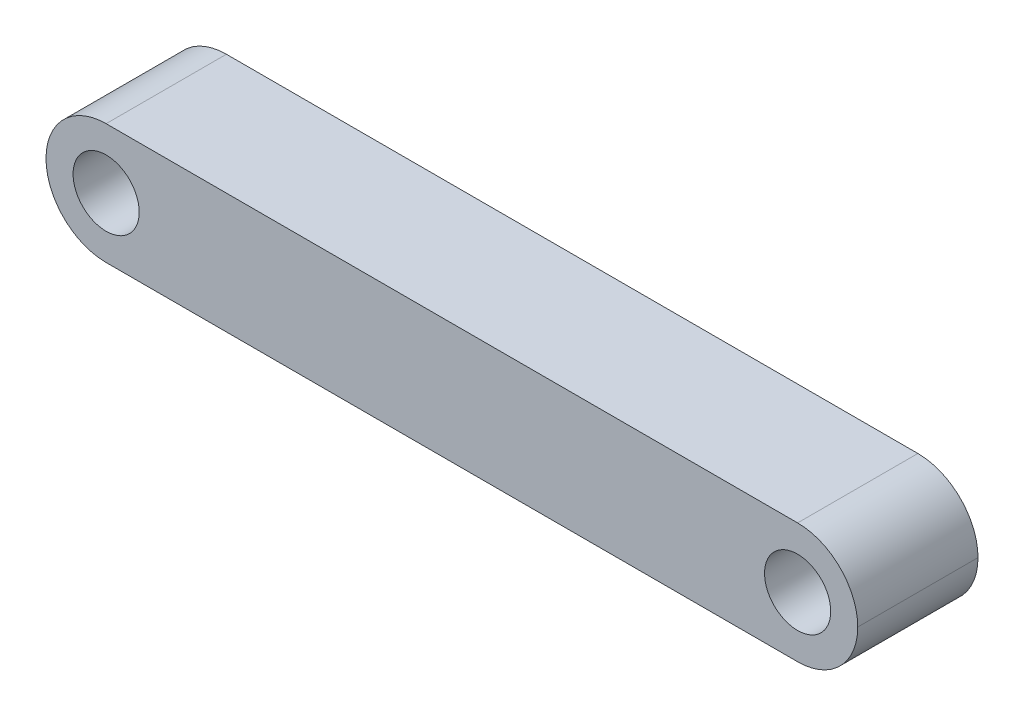
SolidWorks part; units mm, degrees
ref_plane "前视基准面" through (0, 0, 0) normal (0, 0, 1) x (1, 0, 0)
ref_plane "上视基准面" through (0, 0, 0) normal (0, 1, 0) x (1, 0, 0)
ref_plane "右视基准面" through (0, 0, 0) normal (1, 0, 0) x (0, 0, -1)
sketch "草图1" plane through (0, 0, 0) normal (0, 0, 1) x (1, 0, 0)
  line L1 (-13.5, -2) -> (13.5, -2)
  line L2 (-13.5, -2) -> (-13.5, 2)
  line L3 (-13.5, 2) -> (13.5, 2)
  line L4 (13.5, -2) -> (13.5, 2)
  line L5 (-13.5, -2) -> (13.5, 2) construction
  line L6 (-13.5, 2) -> (13.5, -2) construction
  point P0 (0, 0)
  dimension "D1" = 27
  dimension "D2" = 4
extrude "凸台-拉伸1" add sketch "草图1" along normal blind 4
fillet "圆角1" radius 2 4 edges at (-13.5, -2, 2) (-13.5, 2, 2) (13.5, -2, 2) (13.5, 2, 2)
sketch "草图2" plane through (0, 0, 4) normal (0, 0, 1) x (1, 0, 0)
  line L2 (-11.5, -2) -> (11.5, -2)
  line L3 (11.5, 2) -> (-11.5, 2)
  line L4 (-11.5, -2) -> (11.5, -2)
  line L5 (11.5, 2) -> (-11.5, 2)
  circle A0 centre (11.5, 0) radius 1.1
  circle A1 centre (-11.5, 0) radius 1.1
  arc A4 (-11.5, 2) -> (-13.5, 0) centre (-11.5, 0) ccw
  arc A5 (-13.5, 0) -> (-11.5, -2) centre (-11.5, 0) ccw
  arc A6 (11.5, -2) -> (13.5, 0) centre (11.5, 0) ccw
  arc A7 (13.5, 0) -> (11.5, 2) centre (11.5, 0) ccw
  arc A8 (-11.5, 2) -> (-13.5, 0) centre (-11.5, 0) ccw
  arc A9 (-13.5, 0) -> (-11.5, -2) centre (-11.5, 0) ccw
  arc A10 (11.5, -2) -> (13.5, 0) centre (11.5, 0) ccw
  arc A11 (13.5, 0) -> (11.5, 2) centre (11.5, 0) ccw
  dimension "D2" = 2.2
  dimension "D1" = 0
extrude "切除-拉伸1" cut sketch "草图2" against normal blind 13 contours A1 | A0 region at (11.5, 0, 4) region at (-11.5, 0, 4)
